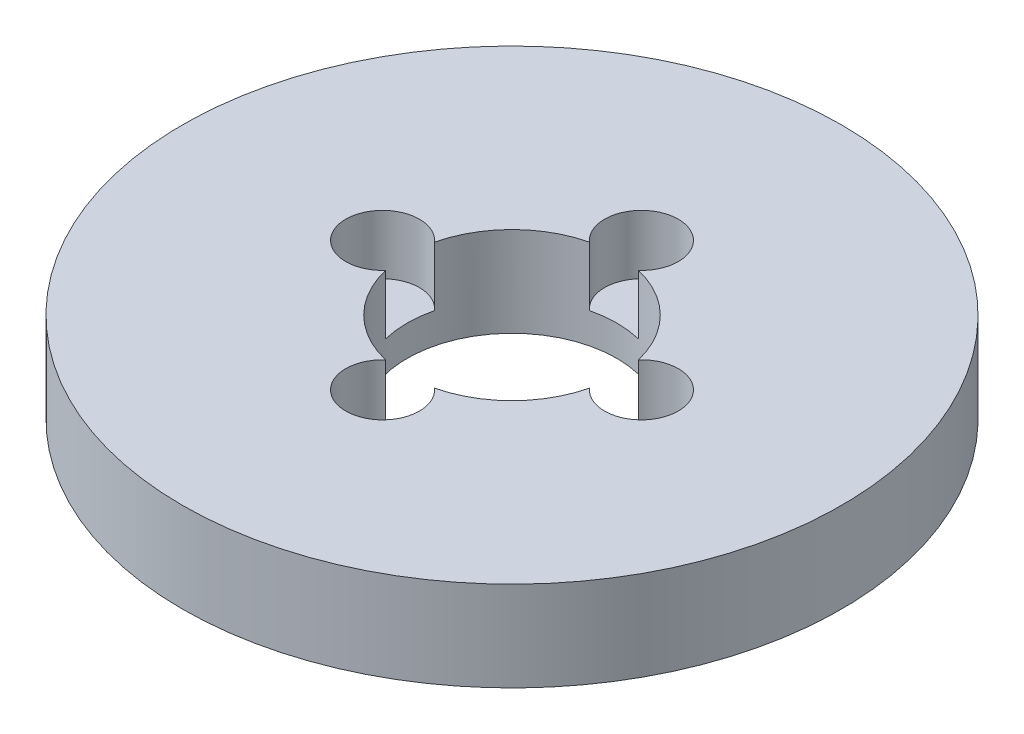
SolidWorks part; units mm, degrees
ref_plane "Front Plane" through (0, 0, 0) normal (0, 0, 1) x (1, 0, 0)
ref_plane "Top Plane" through (0, 0, 0) normal (0, 1, 0) x (1, 0, 0)
ref_plane "Right Plane" through (0, 0, 0) normal (1, 0, 0) x (0, 0, -1)
sketch "Sketch1" plane through (0, 0, 0) normal (0, 1, 0) x (1, 0, 0)
  circle A0 centre (0, 0) radius 55
  dimension "FLANGE_OD" = 110
extrude "Boss-Extrude1" add sketch "Sketch1" along normal blind 15
sketch "Sketch2" plane through (0, 0, 0) normal (0, 1, 0) x (1, 0, 0)
  circle A0 centre (0, 0) radius 17.5
  dimension "BORE_D" = 35
extrude "Cut-Extrude1" cut sketch "Sketch2" along normal through all
sketch "Sketch3" plane through (0, 15, 0) normal (0, 1, 0) x (1, 0, 0)
  circle A0 centre (0, 0) radius 21.6006 construction
  circle A1 centre (-21.6006, 0) radius 6.1458
  dimension "BOLT_D" = 12.2917
  dimension "BOLT_PCD" = 43.2012
extrude "Cut-Extrude2" cut sketch "Sketch3" against normal blind 9.8939
pattern_circular "CirPattern1" count 4 over 360 about axis through (0, 0, 0) along (0, 1, 0) of "Cut-Extrude2"
